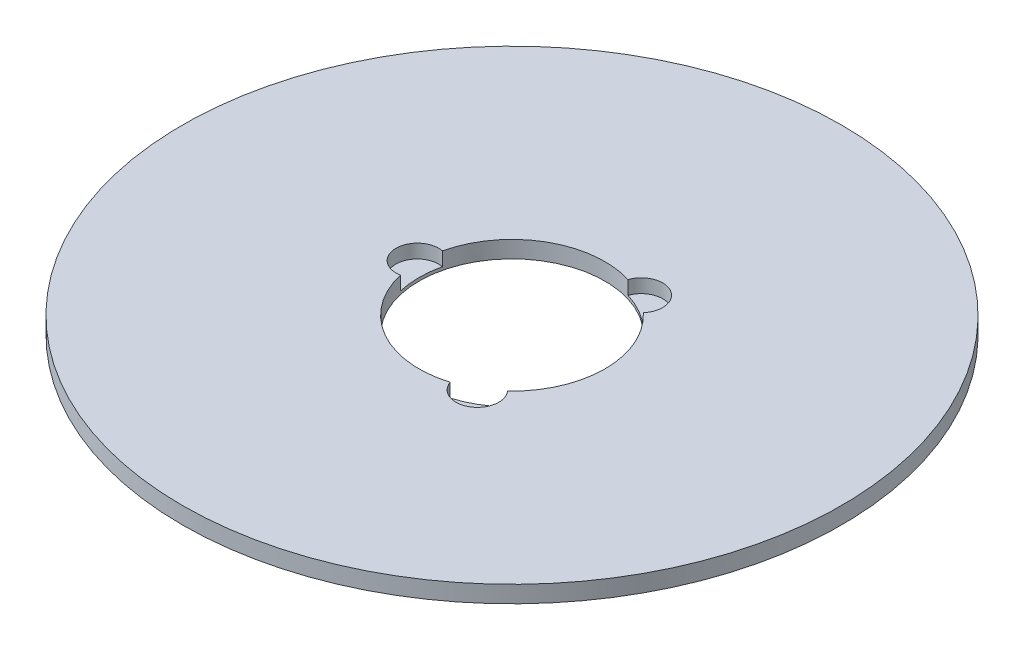
SolidWorks part; units mm, degrees
ref_plane "Front Plane" through (0, 0, 0) normal (0, 0, 1) x (1, 0, 0)
ref_plane "Top Plane" through (0, 0, 0) normal (0, 1, 0) x (1, 0, 0)
ref_plane "Right Plane" through (0, 0, 0) normal (1, 0, 0) x (0, 0, -1)
sketch "Sketch1" plane through (0, 0, 0) normal (0, 1, 0) x (1, 0, 0)
  circle A0 centre (0, 0) radius 97.5
  dimension "FLANGE_OD" = 195
extrude "Boss-Extrude1" add sketch "Sketch1" along normal blind 5
sketch "Sketch2" plane through (0, 0, 0) normal (0, 1, 0) x (1, 0, 0)
  circle A0 centre (0, 0) radius 27.5
  dimension "BORE_D" = 55
extrude "Cut-Extrude1" cut sketch "Sketch2" along normal through all
sketch "Sketch3" plane through (0, 5, 0) normal (0, 1, 0) x (1, 0, 0)
  circle A0 centre (0, 0) radius 28.0132 construction
  circle A1 centre (-28.0132, 0) radius 6.3258
  dimension "BOLT_D" = 12.6517
  dimension "BOLT_PCD" = 56.0265
extrude "Cut-Extrude2" cut sketch "Sketch3" against normal blind 4.0641
pattern_circular "CirPattern1" count 3 over 360 about axis through (0, 0, 0) along (0, 1, 0) of "Cut-Extrude2"
